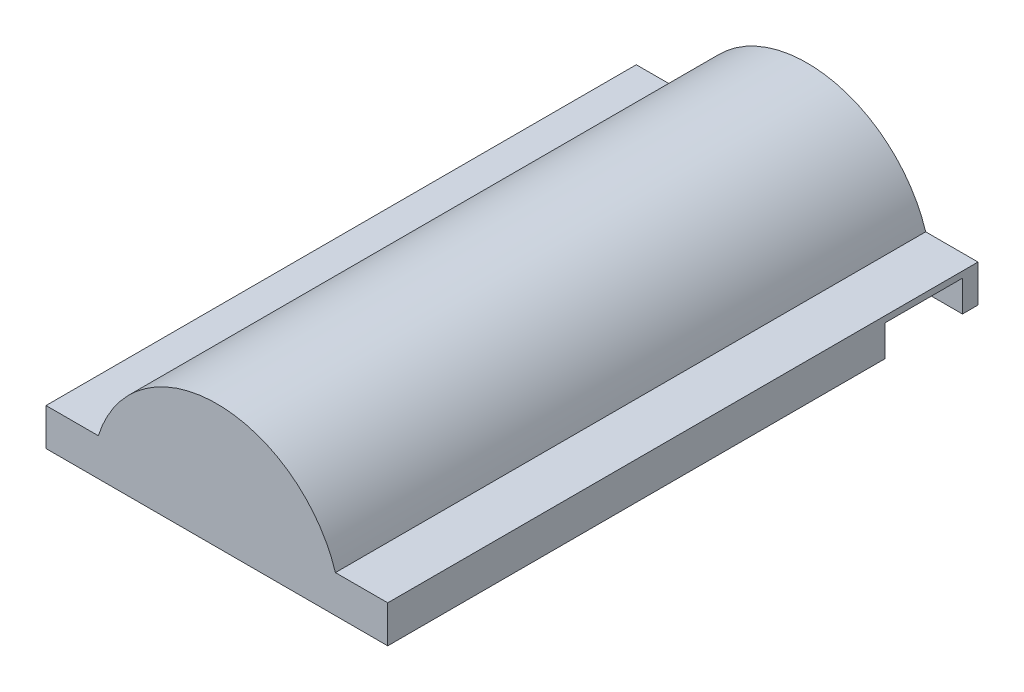
SolidWorks part; units mm, degrees
ref_plane "Front Plane" through (0, 0, 0) normal (0, 0, 1) x (1, 0, 0)
ref_plane "Top Plane" through (0, 0, 0) normal (0, 1, 0) x (1, 0, 0)
ref_plane "Right Plane" through (0, 0, 0) normal (1, 0, 0) x (0, 0, -1)
sketch "Sketch1" plane through (0, 0, 0) normal (0, 0, 1) x (1, 0, 0)
  line L0 (931.5757, 120) -> (1100, 120)
  line L1 (0, 0) -> (1100, 0)
  line L2 (0, 0) -> (0, 120)
  line L3 (0, 120) -> (168.4243, 120)
  line L4 (1100, 0) -> (1100, 120)
  arc A0 (931.5757, 120) -> (168.4243, 120) centre (550, 0) ccw
  dimension "D1" = 800
  dimension "D4" = 550
  dimension "D2" = 1100
  dimension "D3" = 120
extrude "Boss-Extrude1" add sketch "Sketch1" along normal blind 1900
sketch "Sketch2" plane through (0, 0, 1900) normal (0, 0, 1) x (1, 0, 0)
  line L0 (0, 0) -> (1100, 0) construction
  circle A0 centre (550, 0) radius 300
extrude "Cut-Extrude1" cut sketch "Sketch2" against normal through all
sketch "Sketch4" plane through (1100, 0, 0) normal (1, 0, 0) x (0, 0, -1)
  line L0 (-1900, 0) -> (0, 0) construction
  line L1 (-50, 0) -> (-300, 0)
  line L2 (-50, 0) -> (-50, 100)
  line L3 (-50, 100) -> (-300, 100)
  line L4 (-300, 0) -> (-300, 100)
  line L5 (0, 0) -> (0, 120) construction
  line L6 (-1900, 120) -> (0, 120) construction
  dimension "D1" = 250
  dimension "D2" = 50
  dimension "D3" = 20
extrude "Cut-Extrude3" cut sketch "Sketch4" against normal blind 550
shell "Shell1" thickness 20 removed face at (975, 0, 25) removed face at (125, 0, 950) removed face at (696.7752, 100.1826, 562.5) removed face at (975, 0, 1100)
sketch "Sketch5" plane through (0, 0, 0) normal (0, 0, -1) x (-1, 0, 0)
  line L0 (-850, 0) -> (-250, 0)
  arc A0 (-850, 0) -> (-250, 0) centre (-550, 0) cw
  arc M2 (-850, 0) -> (-250, 0) centre (-550, 0) cw
extrude "Boss-Extrude2" add sketch "Sketch5" against normal blind 10 contours L0 M2 region at (550, 127.324, 0)
sketch "Sketch6" plane through (0, 0, 1900) normal (0, 0, 1) x (1, 0, 0)
  line L0 (850, 0) -> (250, 0)
  line L1 (850, 0) -> (250, 0)
  arc A0 (850, 0) -> (250, 0) centre (550, 0) ccw
  arc A1 (850, 0) -> (250, 0) centre (550, 0) ccw construction
  arc A2 (850, 0) -> (250, 0) centre (550, 0) ccw
  arc M1 (250, 0) -> (850, 0) centre (550, 0) cw
extrude "Boss-Extrude3" add sketch "Sketch6" against normal blind 10 contours L0 M1 region at (550, 127.324, 1900)
